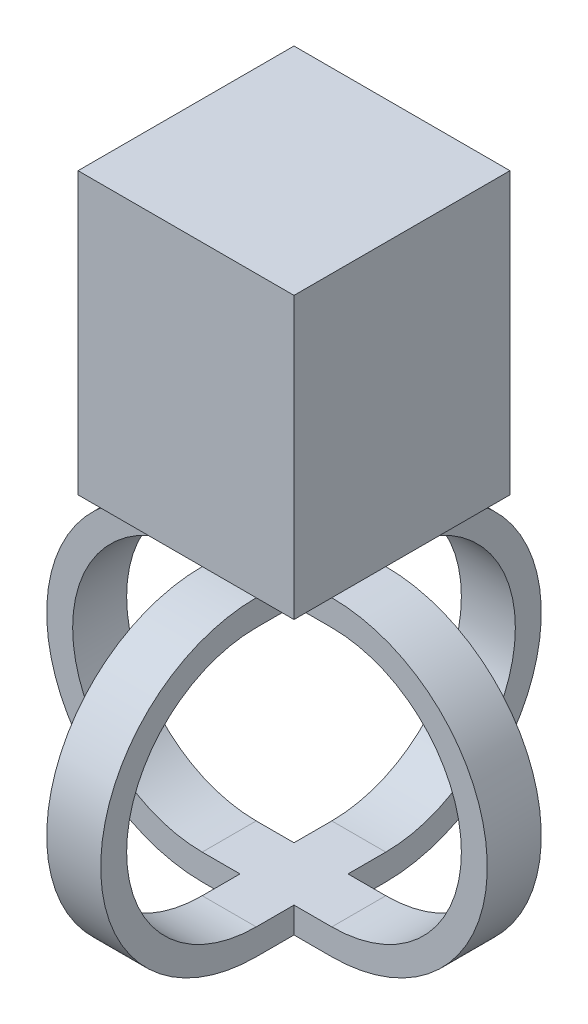
SolidWorks part; units mm, degrees
material "PLA"
ref_plane "Front Plane" through (0, 0, 0) normal (0, 0, 1) x (1, 0, 0)
ref_plane "Top Plane" through (0, 0, 0) normal (0, 1, 0) x (1, 0, 0)
ref_plane "Right Plane" through (0, 0, 0) normal (1, 0, 0) x (0, 0, -1)
sketch "Sketch1" plane through (0, 0, 0) normal (0, 0, 1) x (1, 0, 0)
  line L0 (0, 0) -> (3, 0)
  line L1 (3, 14.4) -> (0, 14.4)
  line L2 (0, 1.2) -> (3, 1.2)
  line L3 (3, 13.2) -> (0, 13.2)
  line L4 (0, 13.2) -> (0, 14.4)
  line L6 (0, 1.2) -> (0, 0)
  arc A0 (3, 0) -> (3, 14.4) centre (3, 7.2) ccw
  arc A1 (3, 1.2) -> (3, 13.2) centre (3, 7.2) ccw
  dimension "D1" = 7.2
  dimension "D2" = 3
  dimension "D3" = 1.2
extrude "Boss-Extrude1" add sketch "Sketch1" along normal mid plane 2.5
ref_axis "Axis1" through (0, 0.1818, 0) along (0, 1, 0)
pattern_circular "CirPattern1" count 4 over 360 about axis through (0, 0.1818, 0) along (0, 1, 0) of "Boss-Extrude1"
sketch "Sketch6" plane through (0, 0, 0) normal (1, 0, 0) x (0, 0, -1)
  line L0 (0, 0.1818) -> (0, 25.6274) construction
  line L1 (0, 7.55) -> (0, 9.1269)
  line L2 (1.25, 14.4) -> (1.25, 13.2) construction
  line L3 (1.25, 0) -> (1.25, 14.4) construction
  line L4 (1.25, 13.2) -> (-1.25, 13.2) construction
  line L5 (0, 20.05) -> (0, 7.55)
  arc A0 (0, 20.05) -> (0, 7.55) centre (0, 13.8) ccw
  point P13 (1.25, 13.8)
  dimension "D1" = 12.5
sketch "Sketch2" plane through (0, 14.4, 0) normal (0, 1, 0) x (1, 0, 0)
  line L1 (-5, 5) -> (5, 5)
  line L2 (-5, 5) -> (-5, -5)
  line L3 (-5, -5) -> (5, -5)
  line L4 (5, 5) -> (5, -5)
  line L5 (-5, 5) -> (5, -5) construction
  line L6 (-5, -5) -> (5, 5) construction
  point P0 (0, 0)
  dimension "D1" = 10
  dimension "D2" = 10
extrude "Boss-Extrude2" add sketch "Sketch2" along normal blind 15 separate body
chamfer "Chamfer1" distance 2 angle 45 4 edges at (0, 14.4, -5) (5, 14.4, 0) (0, 14.4, 5) (-5, 14.4, 0)
equation "\"r\" = 6.5mm'Polmer vzmeti"
equation "\"w\"= 2.5mm'Širina vzmeti"
equation "\"t\"= 0.7mm'Debelina vzmeti"
equation "\"b\"= 3'Ravno področje"
equation "\"D1@Sketch1\"=\"r\"+\"t\""
equation "\"D2@Sketch1\"=\"b\""
equation "\"D1@Boss-Extrude1\"=\"w\""
